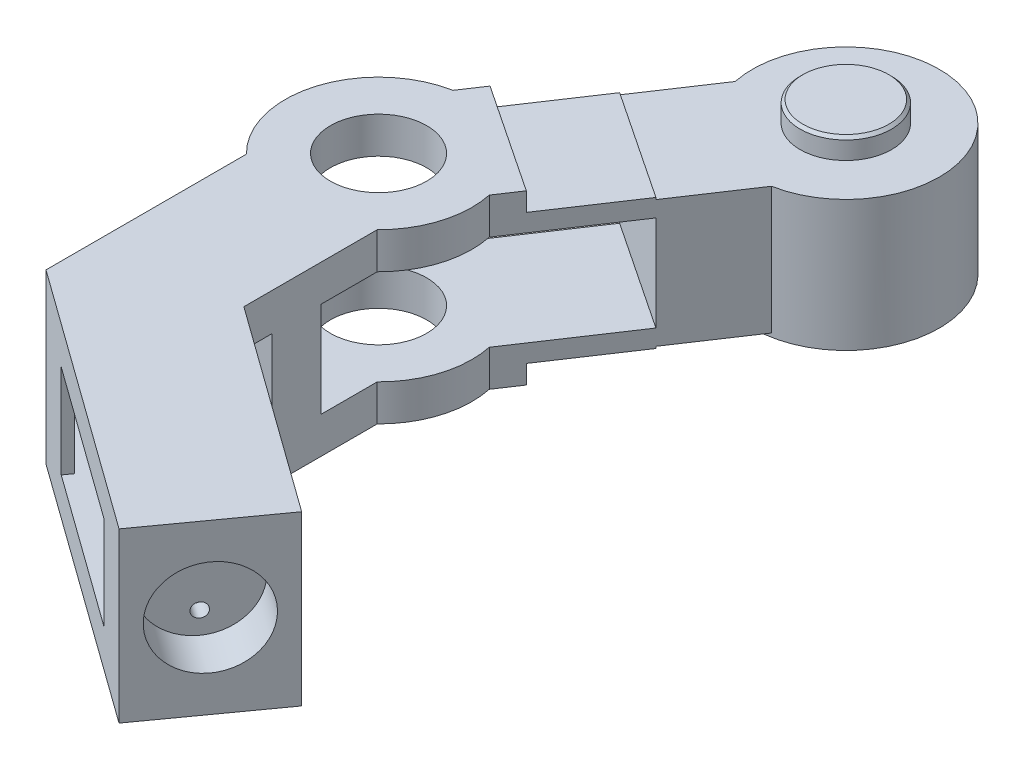
SolidWorks part; units mm, degrees
other "标注1"
sketch "草图14" plane through (-30, -9, -10) normal (-0.5775, -0.0146, -0.8163) x (-0.4018, 0.8755, 0.2686)
other "标注2"
sketch "草图15" plane through (-30, -9, -10) normal (-0.5775, -0.0146, -0.8163) x (-0.4018, 0.8755, 0.2686)
material "6061 合金"
ref_plane "前视基准面" through (0, 0, 0) normal (0, 0, 1) x (1, 0, 0)
ref_plane "上视基准面" through (0, 0, 0) normal (0, 1, 0) x (1, 0, 0)
ref_plane "右视基准面" through (0, 0, 0) normal (1, 0, 0) x (0, 0, -1)
sketch "草图1" plane through (0, 0, 0) normal (0, 1, 0) x (1, 0, 0)
  line L0 (0, 0) -> (-20, -30)
  line L1 (-20, -30) -> (-20, -55)
  line L2 (-20, -55) -> (5, -73)
  dimension "D1" = 30
  dimension "D2" = 25
  dimension "D3" = 18
  dimension "D4" = 20
  dimension "D5" = 25
extrude "拉伸-薄壁1" add sketch "草图1" along normal mid plane 13.6 thin thin type mid plane wall 14
sketch "草图2" plane through (0, 6.8, 0) normal (0, 1, 0) x (1, 0, 0)
  line L0 (-5.8244, 3.8829) -> (5.8244, -3.8829) construction
  line L1 (-27, -27.8806) -> (-13, -32.1194) construction
  circle A0 centre (0, 0) radius 10
  circle A1 centre (-20, -30) radius 10
  dimension "D1" = 20
  dimension "D2" = 20
extrude "凸台-拉伸1" add sketch "草图2" against normal blind 14
sketch "草图3" plane through (0, 0, 0) normal (0, 1, 0) x (1, 0, 0)
  line L0 (-14.7303, -9.4761) -> (-3.0816, -17.2419)
  line L1 (-27, -70.7171) -> (-13, -70.7171)
  line L7 (-13, -51.4144) -> (-13, -37.1414)
  line L8 (-10.2143, -27.9409) -> (1.863, -9.8249)
  line L10 (-27, -37.1414) -> (-27, -58.5856)
  line L11 (-27, -58.5856) -> (0.9099, -78.6807)
  line L12 (0.9099, -78.6807) -> (9.0901, -67.3193)
  line L13 (9.0901, -67.3193) -> (-13, -51.4144)
  line L14 (-13, -51.4144) -> (-13, -37.1414)
  line L17 (-27, -37.1414) -> (-27, -58.5856)
  line L18 (-27, -58.5856) -> (0.9099, -78.6807)
  line L19 (0.9099, -78.6807) -> (9.0901, -67.3193)
  line L20 (9.0901, -67.3193) -> (-13, -51.4144)
  line L23 (-10.2143, -27.9409) -> (1.863, -9.8249)
  line L24 (-9.7857, -2.0591) -> (-21.863, -20.1751)
  line L25 (-9.7857, -2.0591) -> (-21.863, -20.1751)
  arc A3 (-13, -37.1414) -> (-10.2143, -27.9409) centre (-20, -30) ccw
  arc A4 (-13, -37.1414) -> (-10.2143, -27.9409) centre (-20, -30) ccw
  arc A5 (1.863, -9.8249) -> (-9.7857, -2.0591) centre (0, 0) ccw
  arc A9 (1.863, -9.8249) -> (-9.7857, -2.0591) centre (0, 0) ccw
  arc A10 (-21.863, -20.1751) -> (-27, -37.1414) centre (-20, -30) ccw
  arc A11 (-21.863, -20.1751) -> (-27, -37.1414) centre (-20, -30) ccw
  dimension "D1" = 0
extrude "凸台-拉伸2" add sketch "草图3" along normal mid plane 18 contours L25 A11 L17 L1 L14 A4 L23 L0 region at (-14.2793, 0, 44.9217)
sketch "草图4" plane through (0, 0, 0) normal (0, 1, 0) x (1, 0, 0)
  line L0 (-13, -37.1414) -> (-13, -43.1414)
  line L1 (-13, -51.4144) -> (-13, -37.1414) construction
  line L2 (-13, -43.1414) -> (-27, -43.1414)
  line L3 (-27, -37.1414) -> (-27, -58.5856) construction
  line L4 (-27, -43.1414) -> (-27, -37.1414)
  line L6 (-14.7303, -9.4761) -> (-21.863, -20.1751)
  line L7 (-27, -37.1414) -> (-27, -58.5856)
  line L8 (-27, -58.5856) -> (0.9099, -78.6807)
  line L9 (-13, -51.4144) -> (-13, -37.1414)
  line L10 (-10.2143, -27.9409) -> (-3.0816, -17.2419)
  line L11 (-3.0816, -17.2419) -> (-14.7303, -9.4761)
  line L12 (-14.7303, -9.4761) -> (-21.863, -20.1751)
  line L16 (-10.2143, -27.9409) -> (-3.0816, -17.2419)
  line L21 (0.9099, -78.6807) -> (9.0901, -67.3193)
  line L23 (9.0901, -67.3193) -> (-13, -51.4144)
  line L25 (-3.0816, -17.2419) -> (-14.7303, -9.4761)
  arc A2 (-21.863, -20.1751) -> (-27, -37.1414) centre (-20, -30) ccw
  arc A3 (-13, -37.1414) -> (-10.2143, -27.9409) centre (-20, -30) ccw
  arc A4 (-21.863, -20.1751) -> (-27, -37.1414) centre (-20, -30) ccw
  arc A5 (-13, -37.1414) -> (-10.2143, -27.9409) centre (-20, -30) ccw
  dimension "D2" = 6
  dimension "D1" = 0
extrude "切除-拉伸1" cut sketch "草图4" against normal mid plane 10.2
sketch "草图5" plane through (0, 9, 0) normal (0, 1, 0) x (1, 0, 0)
  circle A1 centre (0, 0) radius 4.9
  dimension "D1" = 9.8
extrude "凸台-拉伸3" add sketch "草图5" against normal blind 15
sketch "草图6" plane through (0, 9, 0) normal (0, 1, 0) x (1, 0, 0)
  circle A0 centre (-20, -30) radius 10
  circle A1 centre (-20, -30) radius 5.15
  dimension "D1" = 4.85
extrude "切除-拉伸5" cut sketch "草图6" against normal blind 20 contours A1
sketch "草图7" plane through (-28.8182, 0, 40.0253) normal (0.5843, 0, -0.8115) x (-0.8115, 0, -0.5843)
  line L0 (-19.4917, 5) -> (-39.7119, 5)
  line L1 (-19.4917, 9) -> (-19.4917, -9) construction
  line L2 (-39.7119, 5) -> (-39.7119, -5)
  line L3 (-39.7119, -5) -> (-19.4917, -5)
  line L4 (-19.4917, -5) -> (-19.4917, 5)
  line L5 (-46.7119, 9) -> (-19.4917, 9) construction
  line L6 (-46.7119, -9) -> (-19.4917, -9) construction
  line L7 (-46.7119, 9) -> (-46.7119, -9) construction
  dimension "D1" = 4
  dimension "D2" = 4
  dimension "D3" = 7
sketch "草图8" plane through (0, 9, 0) normal (0, 1, 0) x (1, 0, 0)
  line L0 (3.4094, -63.2291) -> (-4.1866, -73.7791)
  line L1 (3.4094, -63.2291) -> (-13, -51.4144) construction
  line L2 (9.0901, -67.3193) -> (-13, -51.4144) construction
  line L3 (-4.1866, -73.7791) -> (-26, -58.0734)
  line L6 (-26, -48.4144) -> (-26, -58.0734)
  line L8 (-13, -51.4144) -> (3.4094, -63.2291)
  line L9 (0.9099, -78.6807) -> (9.0901, -67.3193) construction
  line L11 (-26, -48.4144) -> (-13, -48.4144)
  line L12 (-13, -51.4144) -> (-13, -37.1414) construction
  line L13 (-13, -48.4144) -> (-13, -51.4144)
  line L17 (-27, -58.5856) -> (0.9099, -78.6807) construction
  line L19 (-27, -37.1414) -> (-27, -58.5856) construction
  dimension "D1" = 7
  dimension "D2" = 3
  dimension "D3" = 1
  dimension "D4" = 1
extrude "切除-拉伸8" cut sketch "草图8" against normal blind 5 and the other way blind 5 from offset 9 offset against normal yes
sketch "草图9" plane through (37.9083, 0, 27.294) normal (0.8115, 0, 0.5843) x (0.5843, 0, -0.8115)
  line L0 (-63.3205, -9) -> (-49.3205, -9) construction
  line L1 (-49.3205, 9) -> (-49.3205, -9) construction
  circle A0 centre (-56.3205, 0) radius 5.15
  dimension "D1" = 9
  dimension "D3" = 10.3
  dimension "D2" = 7
extrude "切除-拉伸9" cut sketch "草图9" against normal blind 5
sketch "草图11" plane through (33.8507, 0, 24.3725) normal (0.8115, 0, 0.5843) x (0.5843, 0, -0.8115)
  circle A0 centre (-56.3205, 2.8) radius 0.75
  circle A1 centre (-56.3205, -2.8) radius 0.75
  circle A2 centre (-56.3205, 0) radius 5.15 construction
  dimension "D1" = 2.8
  dimension "D5" = 1.5
  dimension "D6" = 1.5
  dimension "D2" = 0
  dimension "D3" = 2.8
  dimension "D4" = 0
extrude "切除-拉伸10" cut sketch "草图11" against normal blind 2
sketch "草图12" plane through (0, 9, 0) normal (0, 1, 0) x (1, 0, 0)
  line L0 (-14.7303, -9.4761) -> (-3.0816, -17.2419)
  line L1 (-3.0816, -17.2419) -> (-8.6286, -25.5624)
  line L2 (-10.2143, -27.9409) -> (-3.0816, -17.2419) construction
  line L3 (-8.6286, -25.5624) -> (-20.2774, -17.7966)
  line L4 (-14.7303, -9.4761) -> (-21.863, -20.1751) construction
  line L5 (-20.2774, -17.7966) -> (-14.7303, -9.4761)
  dimension "D1" = 10
extrude "切除-拉伸11" cut sketch "草图12" against normal blind 2
sketch "草图13" plane through (0, -9, 0) normal (0, -1, 0) x (1, 0, 0)
  line L4 (-14.7303, 9.4761) -> (-3.0816, 17.2419)
  line L5 (-3.0816, 17.2419) -> (-8.6286, 25.5624)
  line L6 (-8.6286, 25.5624) -> (-20.2774, 17.7966)
  line L7 (-20.2774, 17.7966) -> (-14.7303, 9.4761)
  line L8 (-14.7303, 9.4761) -> (-3.0816, 17.2419)
  line L9 (-3.0816, 17.2419) -> (-8.6286, 25.5624)
  line L10 (-8.6286, 25.5624) -> (-20.2774, 17.7966)
  line L11 (-20.2774, 17.7966) -> (-14.7303, 9.4761)
  dimension "D1" = 0
extrude "切除-拉伸12" cut sketch "草图13" against normal blind 2
extrude "切除-拉伸14" cut sketch "草图7" against normal blind 14
chamfer "滑动边倒角_C0.3" distance 0.3 angle 45 1 edges at (0, 9, 4.9)
sketch "草图19" plane through (0, -7.2, 0) normal (0, -1, 0) x (1, 0, 0)
  circle A0 centre (0, 0) radius 4.9
  dimension "D1" = 9.8
extrude "另一侧圆柱_直径9.8_外伸2.2" add sketch "草图19" along normal blind 2.2
chamfer "另一侧圆柱端部倒角_C0.3" distance 0.3 angle 45 1 edges at (0, -9.4, -4.9)
